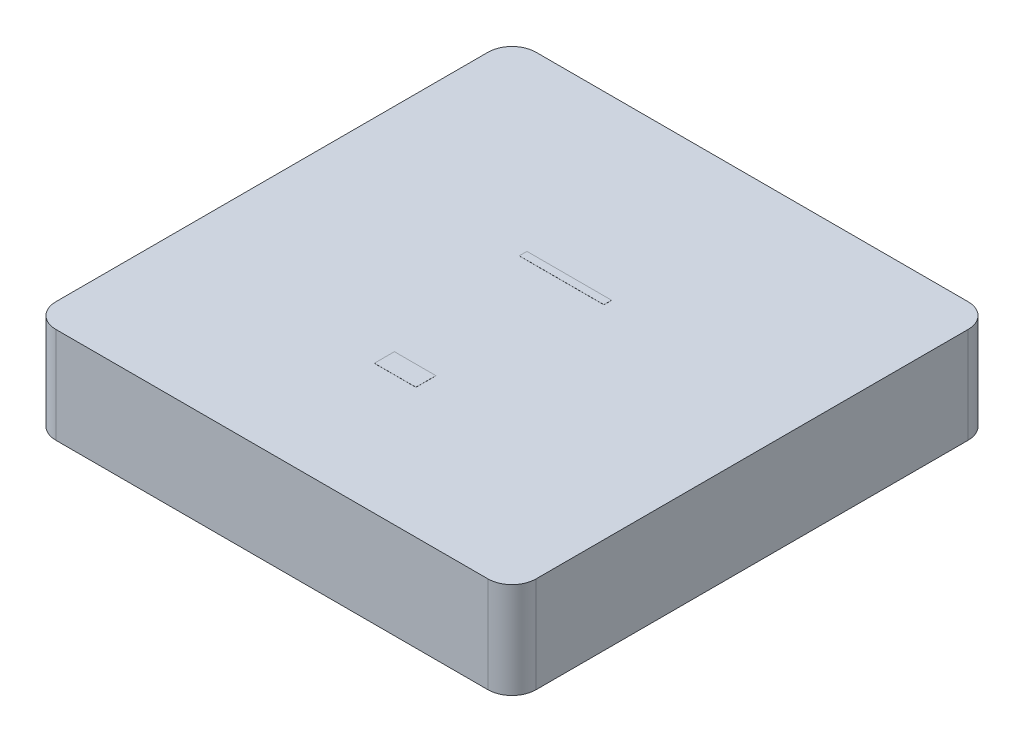
SolidWorks part; units mm, degrees
ref_plane "Front Plane" through (0, 0, 0) normal (0, 0, 1) x (1, 0, 0)
ref_plane "Top Plane" through (0, 0, 0) normal (0, 1, 0) x (1, 0, 0)
ref_plane "Right Plane" through (0, 0, 0) normal (1, 0, 0) x (0, 0, -1)
sketch "Sketch1" plane through (0, 0, 0) normal (0, 1, 0) x (1, 0, 0)
  line L0 (0, 0) -> (12.7, 0)
  line L1 (12.7, 0) -> (12.7, 12.7)
  line L2 (12.7, 12.7) -> (0, 12.7)
  line L3 (0, 12.7) -> (0, 0)
  dimension "D1" = 12.7
  dimension "D2" = 12.7
extrude "Boss-Extrude1" add sketch "Sketch1" along normal blind 2.54
fillet "Fillet1" radius 0.635 4 edges at (0, 1.27, -12.7) (12.7, 1.27, -12.7) (12.7, 1.27, 0) (0, 1.27, 0)
shell "Shell1" thickness 0.635 removed face at (6.35, 0, -6.35)
sketch "Sketch2" plane through (0, 1.905, 0) normal (0, -1, 0) x (-1, 0, 0)
  line L0 (-0.635, 6.35) -> (-12.065, 6.35) construction
  line L1 (-0.635, 12.065) -> (-0.635, 0.635) construction
  line L2 (-12.065, 0.635) -> (-12.065, 12.065) construction
  line L3 (-6.35, 0.635) -> (-6.35, 12.065) construction
  line L4 (-0.635, 0.635) -> (-12.065, 0.635) construction
  line L5 (-12.065, 12.065) -> (-0.635, 12.065) construction
  circle A0 centre (-6.35, 6.35) radius 2.54
  dimension "D1" = 5.08
extrude "Boss-Extrude2" add sketch "Sketch2" along normal up to surface (1.905 mm away) up to face at (6.35, 0, -6.35)
sketch "Sketch4" plane through (0, 2.54, 0) normal (0, 1, 0) x (1, 0, 0)
  line L0 (0, 12.065) -> (0, 0.635) construction
  line L1 (12.065, 12.7) -> (0.635, 12.7) construction
  line L2 (0.635, 0) -> (12.065, 0) construction
  text T0 "<b>-</b>"
  text T1 "<b>_</b>"
  dimension "D1" = 5.08
  dimension "D2" = 5.2578
  dimension "D3" = 4.318
  dimension "D4" = 2.54
extrude "Boss-Extrude4" add sketch "Sketch4" along normal blind 0.0025
